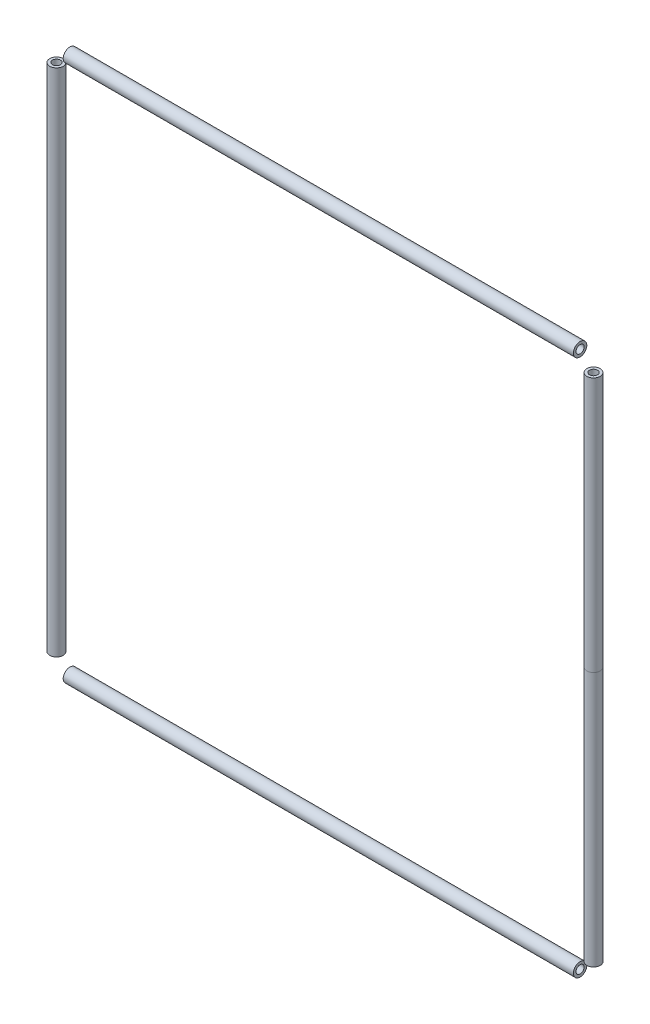
SolidWorks part; units mm, degrees
ref_plane "Front Plane" through (0, 0, 0) normal (0, 0, 1) x (1, 0, 0)
ref_plane "Top Plane" through (0, 0, 0) normal (0, 1, 0) x (1, 0, 0)
ref_plane "Right Plane" through (0, 0, 0) normal (1, 0, 0) x (0, 0, -1)
sketch "Sketch1" plane through (0, 0, 0) normal (0, 0, 1) x (1, 0, 0)
  line L1 (-127, 127) -> (127, 127)
  line L2 (-127, 127) -> (-127, -127)
  line L3 (-127, -127) -> (127, -127)
  line L4 (127, 127) -> (127, -127)
  line L5 (-127, 127) -> (127, -127) construction
  line L6 (-127, -127) -> (127, 127) construction
  point P0 (0, 0)
  dimension "D1" = 254
sketch "Sketch3" plane through (0, 0, 0) normal (0, 1, 0) x (1, 0, 0)
  circle A0 centre (127, 0) radius 3.175
  circle A1 centre (127, 0) radius 1.905
  dimension "D1" = 6.35
  dimension "D2" = 1.27
sweep "Sweep1" add profiles "Sketch3" path "Sketch1"
sketch "Sketch4" plane through (0, 0, 0) normal (0, 0, 1) x (1, 0, 0)
  line L0 (-127, -127) -> (127, 127) construction
  line L1 (133.35, 133.35) -> (120.65, 133.35)
  line L2 (133.35, 133.35) -> (133.35, 120.65)
  line L3 (133.35, 120.65) -> (120.65, 120.65)
  line L4 (120.65, 133.35) -> (120.65, 120.65)
  line L5 (127, 120.65) -> (127, 133.35) construction
  line L6 (133.35, 127) -> (120.65, 127) construction
  line L7 (-127, 127) -> (127, -127) construction
  line L8 (-133.35, 133.35) -> (-120.65, 133.35)
  line L9 (-133.35, 133.35) -> (-133.35, 120.65)
  line L10 (-133.35, 120.65) -> (-120.65, 120.65)
  line L11 (-120.65, 133.35) -> (-120.65, 120.65)
  line L12 (-127, 120.65) -> (-127, 133.35) construction
  line L13 (-133.35, 127) -> (-120.65, 127) construction
  line L15 (-133.35, -133.35) -> (-120.65, -133.35)
  line L16 (-133.35, -133.35) -> (-133.35, -120.65)
  line L17 (-133.35, -120.65) -> (-120.65, -120.65)
  line L18 (-120.65, -133.35) -> (-120.65, -120.65)
  line L19 (-127, -120.65) -> (-127, -133.35) construction
  line L20 (-133.35, -127) -> (-120.65, -127) construction
  line L21 (133.35, -133.35) -> (120.65, -133.35)
  line L22 (133.35, -133.35) -> (133.35, -120.65)
  line L23 (133.35, -120.65) -> (120.65, -120.65)
  line L24 (120.65, -133.35) -> (120.65, -120.65)
  line L25 (127, -120.65) -> (127, -133.35) construction
  line L26 (133.35, -127) -> (120.65, -127) construction
  point P0 (127, 127)
  point P6 (-127, 127)
  point P12 (-127, -127)
  point P16 (127, -127)
  point P20 (118.318, -118.318)
  point P21 (0, 0)
  point P22 (0, 0)
  point P23 (-119.769, -119.769)
  point P24 (-134.0304, -134.0304)
  dimension "D1" = 12.7
extrude "Cut-Extrude1" cut sketch "Sketch4" against normal through all both and the other way through all
